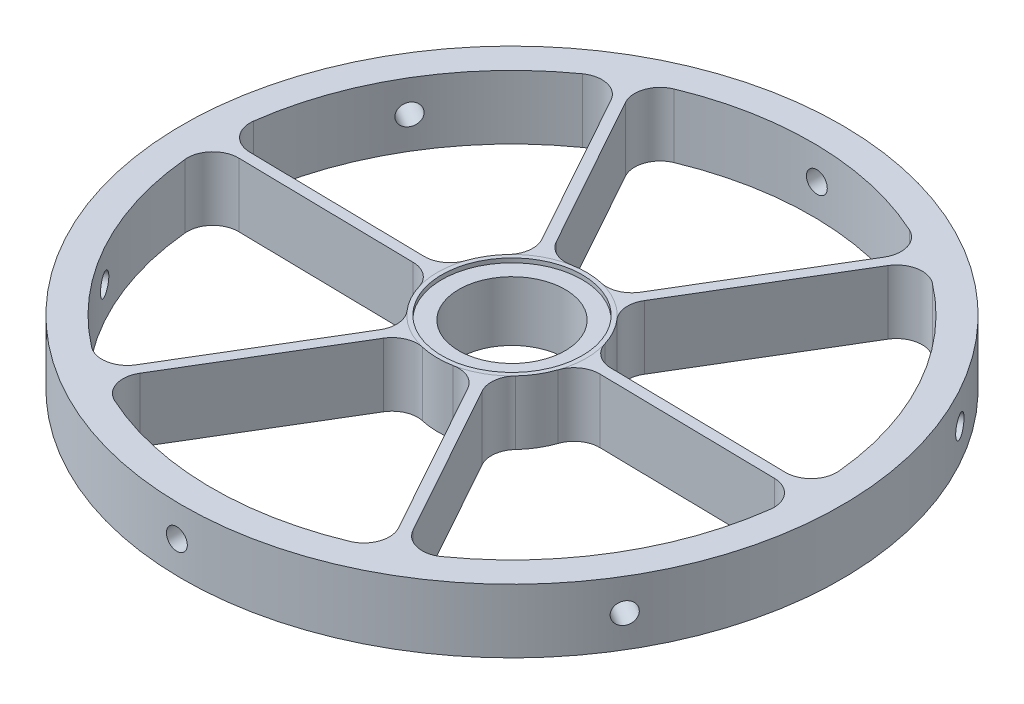
SolidWorks part; units mm, degrees
material "6061-T6 (SS)"
ref_plane "Front Plane" through (0, 0, 0) normal (0, 0, 1) x (1, 0, 0)
ref_plane "Top Plane" through (0, 0, 0) normal (0, 1, 0) x (1, 0, 0)
ref_plane "Right Plane" through (0, 0, 0) normal (1, 0, 0) x (0, 0, -1)
sketch "Center Ring" plane through (0, 0, 0) normal (0, 1, 0) x (1, 0, 0)
  circle A0 centre (0, 0) radius 15.875
  circle A1 centre (0, 0) radius 22.225
  dimension "D2" = 31.75
  dimension "D1" = 6.35
extrude "Center" add sketch "Center Ring" along normal mid plane 19.05
sketch "Outer " plane through (0, 0, 0) normal (0, 1, 0) x (1, 0, 0)
  circle A0 centre (0, 0) radius 98.425
  circle A1 centre (0, 0) radius 89.535
  dimension "D2" = 196.85
  dimension "D1" = 8.89
extrude "Outer Ring" add sketch "Outer " along normal mid plane 19.05 separate body
ref_plane "Plane1" through (0, 0, 47.625) normal (0, 0, 1) x (1, 0, 0)
sketch "beeam" plane through (0, 0, 47.625) normal (0, 0, 1) x (1, 0, 0)
  line L1 (-1.5875, -9.525) -> (1.5875, -9.525)
  line L2 (-1.5875, -9.525) -> (-1.5875, 9.525)
  line L3 (-1.5875, 9.525) -> (1.5875, 9.525)
  line L4 (1.5875, -9.525) -> (1.5875, 9.525)
  line L5 (-1.5875, -9.525) -> (1.5875, 9.525) construction
  line L6 (-1.5875, 9.525) -> (1.5875, -9.525) construction
  point P0 (0, 0)
  dimension "D1" = 3.175
  dimension "D2" = 19.05
extrude "Beam" add sketch "beeam" against normal up to surface and the other way up to surface up to face at (0, 9.525, 22.225) other way up to face at (0, 9.525, 89.535)
pattern_circular "CirPattern1" count 6 over 360 about axis through (0, 9.525, 0) along (0, -1, 0) of "Beam"
ref_plane "Plane2" through (0, 0, 100.0125) normal (0, 0, 1) x (1, 0, 0)
fillet "Fillet1" radius 7.62 24 edges at (78.3211, 0, 43.3856) (76.7336, 0, 46.1353) (-18.4045, 0, -12.4589) (-1.5875, 0, -22.1682) (1.5875, 0, -22.1682) (18.4045, 0, -12.4589) (19.992, 0, -9.7093) (19.992, 0, 9.7093) (18.4045, 0, 12.4589) (1.5875, 0, 22.1682) (-18.4045, 0, 12.4589) (-1.5875, 0, 22.1682) (-19.992, 0, 9.7093) (-19.992, 0, -9.7093) (1.5875, 0, 89.5209) (-1.5875, 0, 89.5209) (-76.7336, 0, 46.1353) (-78.3211, 0, 43.3856) (78.3211, 0, -43.3856) (76.7336, 0, -46.1353) (1.5875, 0, -89.5209) (-1.5875, 0, -89.5209) (-76.7336, 0, -46.1353) (-78.3211, 0, -43.3856)
sketch "Sketch9" plane through (0, 9.525, 0) normal (0, 1, 0) x (1, 0, 0)
  circle A0 centre (0, 0) radius 15.875
  dimension "D1" = 31.75
sketch "Sketch10" plane through (0, 9.525, 0) normal (0, 1, 0) x (1, 0, 0)
  circle A0 centre (0, 0) radius 22.225
  dimension "D1" = 44.45
split line "Split Line2"
ref_plane "Plane4" through (49.2125, 0, 85.2386) normal (0.5, 0, 0.866) x (0, -1, 0)
sketch "Sketch20" plane through (0, 0, 0) normal (0, 1, 0) x (1, 0, 0)
  line L1 (52.1812, -72.7574) -> (35.6077, -82.1499)
  arc A1 (10.064, -88.9676) -> (72.0162, -53.1995) centre (0, 0) ccw construction
  arc A2 (52.1812, -72.7574) -> (35.6077, -82.1499) centre (0, 0) cw
  point P3 (52.1812, -72.7574)
  point P9 (36.9386, -81.5601)
  dimension "D1" = 19.05
ref_plane "Plane6" through (0, 9.525, 0) normal (0, 1, 0) x (1, 0, 0)
sketch "Sketch27" plane through (0, 9.525, 0) normal (0, 1, 0) x (1, 0, 0)
  circle A1 centre (0, 0) radius 20.955
  arc A4 (-6.8566, 21.1409) -> (-14.8802, 16.5085) centre (0, 0) ccw construction
  dimension "05" = 1.27
extrude "Cut-Extrude3" cut sketch "Sketch27" against normal blind 1.27
ref_plane "Plane7" through (0, 0, 0) normal (0, 1, 0) x (1, 0, 0)
sketch "Sketch31" plane through (49.2125, 0, 85.2386) normal (0.5, 0, 0.866) x (0, -1, 0)
  circle A0 centre (0, 0) radius 3.175
  point P3 (3.175, 0)
  dimension "D1" = 6.35
extrude "Cut-Extrude5" cut sketch "Sketch31" against normal up to next
pattern_circular "CirPattern5" count 6 over 360 about axis through (0, 9.525, 0) along (0, -1, 0) of "Cut-Extrude5"
move or copy body "Body-Move/Copy7" bodies to move or copy 127 copy no rotation origin (0, 0, 0) rotation axis (0, -1, 0) rotation angle 31
equation "\"a\"= .125'Width of the Beams"
equation "\"D1@beeam\" = \"a\""
equation "\"T\"= .35'Width of the Outer Ring"
equation "\"D1@Outer \" = \"T\""
equation "\"R\"= .25'Thickness of the Center"
equation "\"D1@Center Ring\" = \"R\""
equation "\"H\"= .75'Height (Outer Ring/Center)"
equation "\"D1@Outer Ring\"= \"H\""
equation "\"D1@Center\"=\"H\""
equation "\"I\"= .75'Height (Beams)"
equation "\"N\"= 6'Number of Beams"
equation "\"D1@CirPattern1\"=\"N\""
equation "\"D2@beeam\"=\"I\""
equation "\"D\"= 1.5'Diameter of the Center"
